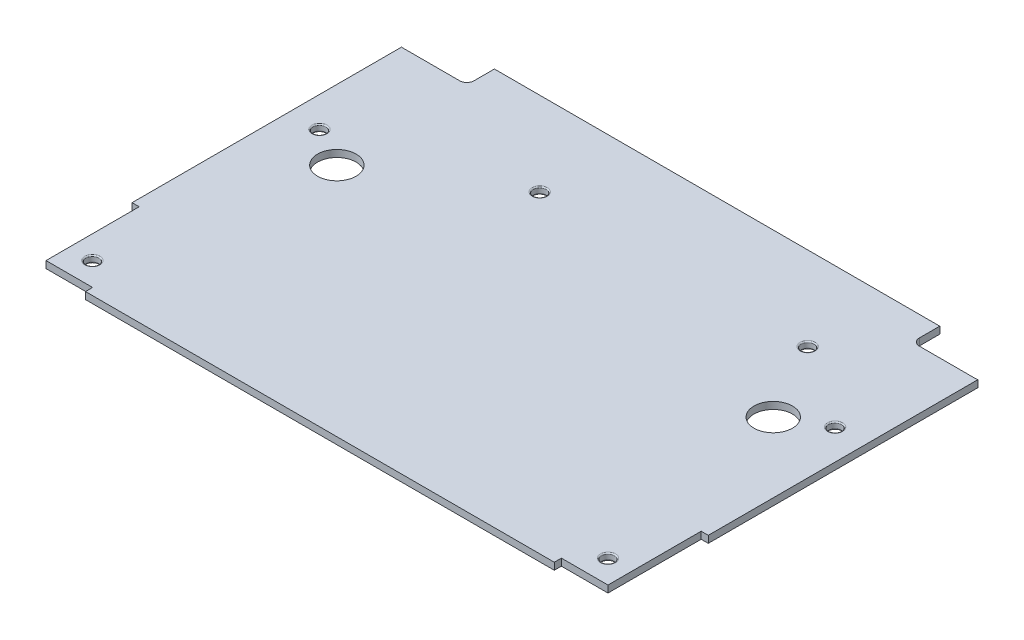
SolidWorks part; units mm, degrees
ref_plane "Front Plane" through (0, 0, 0) normal (0, 0, 1) x (1, 0, 0)
ref_plane "Top Plane" through (0, 0, 0) normal (0, 1, 0) x (1, 0, 0)
ref_plane "Right Plane" through (0, 0, 0) normal (1, 0, 0) x (0, 0, -1)
sketch "Sketch1" plane through (0, 0, 0) normal (0, 1, 0) x (1, 0, 0)
  line L1 (-123.65, -85.2375) -> (123.65, -85.2375)
  line L2 (-123.65, -85.2375) -> (-123.65, 85.2375)
  line L3 (-123.65, 85.2375) -> (123.65, 85.2375)
  line L4 (123.65, -85.2375) -> (123.65, 85.2375)
  line L5 (-123.65, -85.2375) -> (123.65, 85.2375) construction
  line L6 (-123.65, 85.2375) -> (123.65, -85.2375) construction
  point P0 (0, 0)
  dimension "D1" = 247.3
  dimension "D2" = 170.475
extrude "Boss-Extrude1" add sketch "Sketch1" along normal blind 3
sketch "Sketch4" plane through (0, 3, 0) normal (0, 1, 0) x (1, 0, 0)
  line L0 (0, 0) -> (0, -50000) construction
  line L5 (120.6, -82.1875) -> (100.6, -85.2375) construction
  line L15 (-123.65, -85.2375) -> (-120.6, -85.2375)
  line L16 (-123.65, -85.2375) -> (-123.65, -42.1875)
  line L21 (-123.65, -42.1875) -> (-120.6, -42.1875)
  line L23 (-120.6, -82.1875) -> (-120.6, -42.1875)
  line L24 (-123.65, -85.2375) -> (-120.6, -42.1875) construction
  line L25 (-123.65, -42.1875) -> (-120.6, -85.2375) construction
  line L34 (0, 0) -> (50000, 0) construction
  line L35 (-120.6, -85.2375) -> (-100.6, -85.2375)
  line L37 (-120.6, -82.1875) -> (-100.6, -82.1875)
  line L38 (-100.6, -85.2375) -> (-100.6, -82.1875)
  line L39 (-120.6, -85.2375) -> (-100.6, -82.1875) construction
  line L40 (-120.6, -82.1875) -> (-100.6, -85.2375) construction
  line L41 (120.6, -85.2375) -> (100.6, -82.1875) construction
  line L42 (123.65, -42.1875) -> (120.6, -85.2375) construction
  line L43 (123.65, -85.2375) -> (120.6, -42.1875) construction
  line L44 (100.6, -85.2375) -> (100.6, -82.1875)
  line L45 (120.6, -82.1875) -> (100.6, -82.1875)
  line L46 (120.6, -85.2375) -> (100.6, -85.2375)
  line L47 (120.6, -82.1875) -> (120.6, -42.1875)
  line L48 (123.65, -42.1875) -> (120.6, -42.1875)
  line L49 (123.65, -85.2375) -> (123.65, -42.1875)
  line L50 (123.65, -85.2375) -> (120.6, -85.2375)
  point P4 (-122.125, -63.7125)
  point P9 (-110.6, -83.7125)
  point P19 (110.6, -83.7125)
  point P20 (122.125, -63.7125)
  dimension "D1" = 43.05
  dimension "D2" = 3.05
  dimension "D3" = 3.05
  dimension "D4" = 23.05
extrude "Cut-Extrude2" cut sketch "Sketch4" against normal through all
sketch "Sketch2" plane through (0, 3, 0) normal (0, 1, 0) x (1, 0, 0)
  line L0 (0, 0) -> (50000, 0) construction
  line L1 (0, 0) -> (0, 50000) construction
  line L2 (-123.65, 85.2375) -> (-123.65, -42.1875) construction
  line L3 (123.65, 85.2375) -> (-123.65, 85.2375) construction
  line L4 (-100.6, -85.2375) -> (100.6, -85.2375) construction
  circle A0 centre (-110.65, 25.2375) radius 2.75
  circle A1 centre (110.65, 25.2375) radius 2.75
  circle A4 centre (-110.65, -72.2375) radius 2.75
  circle A5 centre (110.65, -72.2375) radius 2.75
  dimension "D1" = 5.5
  dimension "D2" = 13
  dimension "D3" = 60
  dimension "D4" = 13
extrude "Cut-Extrude1" cut sketch "Sketch2" against normal through all
fillet "Fillet1" radius 0.5 8 edges at (-110.65, 3, -22.4875) (-110.65, 0, -22.4875) (110.65, 3, -27.9875) (110.65, 0, -27.9875) (-110.65, 3, 74.9875) (-110.65, 0, 74.9875) (110.65, 3, 69.4875) (110.65, 0, 69.4875)
sketch "Sketch5" plane through (0, 3, 0) normal (0, 1, 0) x (1, 0, 0)
  line L5 (-10, 35.175) -> (10, 35.175)
  line L6 (15.05, 40.225) -> (15.05, 85.2375)
  line L8 (-15.05, 85.2375) -> (-15.05, 40.225)
  line L9 (-10, 35.225) -> (10, 35.225)
  line L10 (15, 40.225) -> (15, 92.225)
  line L11 (15, 92.225) -> (-15, 92.225)
  line L12 (-15, 92.225) -> (-15, 40.225)
  line L13 (-10, 35.225) -> (10, 35.225) construction
  line L14 (15, 40.225) -> (15, 92.225) construction
  line L15 (15, 92.225) -> (-15, 92.225) construction
  line L16 (-15, 92.225) -> (-15, 40.225) construction
  line L17 (15.05, 92.275) -> (-15.05, 92.275) construction
  line L18 (-15.05, 85.2375) -> (15.05, 85.2375)
  line L19 (123.65, 85.2375) -> (-123.65, 85.2375) construction
  line L20 (15.05, 40.225) -> (15.05, 92.275) construction
  line L21 (-15.05, 92.275) -> (-15.05, 40.225) construction
  arc A2 (10, 35.175) -> (15.05, 40.225) centre (10, 40.225) ccw
  arc A3 (-15.05, 40.225) -> (-10, 35.175) centre (-10, 40.225) ccw
  arc A4 (10, 35.225) -> (15, 40.225) centre (10, 40.225) ccw
  arc A5 (-15, 40.225) -> (-10, 35.225) centre (-10, 40.225) ccw
  arc A6 (10, 35.225) -> (15, 40.225) centre (10, 40.225) ccw construction
  arc A7 (-15, 40.225) -> (-10, 35.225) centre (-10, 40.225) ccw construction
  dimension "D1" = 0
  dimension "D2" = 0.05
extrude "Cut-Extrude3" [suppressed] cut sketch "Sketch5" against normal through all
sketch "Sketch6" [suppressed] plane through (0, 3, 0) normal (0, 1, 0) x (1, 0, 0)
  line L0 (-123.65, 105.2375) -> (-123.65, -62.1875) construction
  line L1 (-123.65, -72.4875) -> (-98.57, -72.4875)
  line L2 (-123.65, -72.4875) -> (-123.65, -8.8875)
  line L3 (-123.65, -8.8875) -> (-98.57, -8.8875)
  line L4 (-95.57, -69.4875) -> (-95.57, -11.8875)
  line L5 (-100.6, -105.2375) -> (100.6, -105.2375) construction
  line L6 (0, 0) -> (0, -50000) construction
  line L7 (95.57, -69.4875) -> (95.57, -11.8875)
  line L8 (123.65, -8.8875) -> (98.57, -8.8875)
  line L9 (123.65, -72.4875) -> (123.65, -8.8875)
  line L10 (123.65, -72.4875) -> (98.57, -72.4875)
  arc A0 (98.57, -72.4875) -> (95.57, -69.4875) centre (98.57, -69.4875) cw
  arc A1 (95.57, -11.8875) -> (98.57, -8.8875) centre (98.57, -11.8875) cw
  arc A2 (-98.57, -72.4875) -> (-95.57, -69.4875) centre (-98.57, -69.4875) ccw
  arc A3 (-95.57, -11.8875) -> (-98.57, -8.8875) centre (-98.57, -11.8875) ccw
  point P17 (95.57, -72.4875)
  point P20 (95.57, -8.8875)
  point P23 (-95.57, -72.4875)
  point P26 (-95.57, -8.8875)
  dimension "D4" = 3
  dimension "D1" = 32.75
  dimension "D2" = 63.6
  dimension "D3" = 28.08
extrude "Cut-Extrude4" [suppressed] cut sketch "Sketch6" against normal through all
sketch "Sketch8" [suppressed] plane through (0, 3, 0) normal (0, 1, 0) x (1, 0, 0)
  line L0 (-14.35, -33.2375) -> (-14.35, 49966.7625) construction
  line L1 (53.65, -55.2375) -> (-82.35, -55.2375) construction
  line L2 (53.65, -55.2375) -> (53.65, -11.2375) construction
  line L3 (53.65, -11.2375) -> (-82.35, -11.2375) construction
  line L4 (-82.35, -55.2375) -> (-82.35, -11.2375) construction
  line L5 (53.65, -55.2375) -> (-82.35, -11.2375) construction
  line L6 (53.65, -11.2375) -> (-82.35, -55.2375) construction
  line L7 (-14.35, -33.2375) -> (-50014.35, -33.2375) construction
  circle A0 centre (19.65, -55.2375) radius 1.5
  circle A1 centre (-14.35, -55.2375) radius 1.5
  circle A2 centre (-48.35, -55.2375) radius 1.5
  circle A3 centre (-48.35, -11.2375) radius 1.5
  circle A4 centre (-14.35, -11.2375) radius 1.5
  circle A5 centre (19.65, -11.2375) radius 1.5
  point P4 (-14.35, -33.2375)
  dimension "D1" = 3
  dimension "D3" = 34
extrude "Cut-Extrude6" [suppressed] cut sketch "Sketch8" against normal through all
fillet "Fillet2" [suppressed] radius 0.5
sketch "Sketch9" [suppressed] plane through (0, 3, 0) normal (0, 1, 0) x (1, 0, 0)
  circle A2 centre (-74.85, 26.2625) radius 2.75 construction
  circle A5 centre (40.15, 26.2625) radius 2.75 construction
  circle A8 centre (-74.85, 26.2625) radius 2.75
  circle A11 centre (40.15, 26.2625) radius 2.75
extrude "Cut-Extrude7" [suppressed] cut sketch "Sketch9" against normal through all
fillet "Fillet3" [suppressed] radius 0.5
sketch "Sketch10" plane through (0, 3, 0) normal (0, 1, 0) x (1, 0, 0)
  circle A0 centre (74.85, 49.2625) radius 2.75 construction
  circle A1 centre (-40.15, 49.2625) radius 2.75 construction
  circle A2 centre (74.85, 49.2625) radius 2.75
  circle A3 centre (-40.15, 49.2625) radius 2.75
extrude "Cut-Extrude8" cut sketch "Sketch10" against normal through all
fillet "Fillet4" radius 0.5 4 edges at (-40.15, 3, -46.5125) (-40.15, 0, -46.5125) (74.85, 3, -46.5125) (74.85, 0, -46.5125)
sketch "Sketch11" [suppressed] plane through (0, 3, 0) normal (0, 1, 0) x (1, 0, 0)
  line L0 (-123.65, 43.775) -> (-123.65, -0.725) construction
  line L1 (-83.65, 14.225) -> (-33.65, 14.225)
  line L6 (-83.65, 14.225) -> (-83.65, -35.775)
  line L8 (-83.65, -35.775) -> (-33.65, -35.775)
  line L9 (-33.65, 14.225) -> (-33.65, -35.775)
  line L10 (-83.65, 14.225) -> (-33.65, -35.775) construction
  line L11 (-83.65, -35.775) -> (-33.65, 14.225) construction
  circle A8 centre (-78.65, -30.775) radius 2.75
  circle A9 centre (-110.65, -30.775) radius 2.75 construction
  circle A10 centre (-110.65, -30.775) radius 2.75 construction
  circle A11 centre (-78.65, 9.225) radius 2.75
  circle A12 centre (-38.65, 9.225) radius 2.75
  circle A13 centre (-38.65, -30.775) radius 2.75
  point P4 (-58.65, -10.775)
  point P21 (-58.65, -10.775)
  dimension "D3" = 5
  dimension "D4" = 5.5
  dimension "D1" = 50
  dimension "D2" = 40
  dimension "D5" = 4
extrude "Cut-Extrude9" [suppressed] cut sketch "Sketch11" against normal through all contours A11 | A8 | A13 | A12
fillet "Fillet5" [suppressed] radius 0.5
sketch "Sketch12" [suppressed] plane through (0, 0, 0) normal (0, -1, 0) x (1, 0, 0)
  line L0 (0, 0) -> (0, 50000) construction
  line L4 (98.625, -155.4145) -> (122.675, -155.4145)
  line L5 (125.675, -152.4145) -> (125.675, -94.9145)
  line L6 (122.675, -91.9145) -> (98.625, -91.9145)
  line L7 (95.625, -94.9145) -> (95.625, -152.4145)
  line L9 (125.675, -105.2375) -> (125.675, -94.9145) construction
  line L10 (122.675, -91.9145) -> (98.625, -91.9145) construction
  line L11 (95.625, -94.9145) -> (95.625, -105.2375) construction
  line L12 (123.65, -105.2375) -> (-123.65, -105.2375) construction
  line L13 (123.65, -105.2375) -> (-123.65, -105.2375) construction
  line L15 (125.725, -105.2375) -> (125.725, -94.9145)
  line L16 (122.675, -91.8645) -> (98.625, -91.8645)
  line L17 (95.575, -94.9145) -> (95.575, -105.2375)
  line L18 (95.625, -105.2375) -> (125.675, -105.2375) construction
  line L19 (95.575, -105.2875) -> (125.725, -105.2875) construction
  line L20 (95.575, -105.2375) -> (125.725, -105.2375)
  line L21 (125.725, -105.2875) -> (125.725, -94.9145) construction
  line L22 (95.575, -94.9145) -> (95.575, -105.2875) construction
  line L23 (95.625, -152.4145) -> (95.625, -94.9145) construction
  line L24 (-95.625, -94.9145) -> (-95.625, -105.2375) construction
  line L25 (-122.675, -91.9145) -> (-98.625, -91.9145) construction
  line L26 (-125.675, -105.2375) -> (-125.675, -94.9145) construction
  line L27 (-95.575, -105.2375) -> (-125.725, -105.2375)
  line L28 (-95.575, -94.9145) -> (-95.575, -105.2375)
  line L29 (-122.675, -91.8645) -> (-98.625, -91.8645)
  line L30 (-125.725, -105.2375) -> (-125.725, -94.9145)
  arc A0 (125.725, -94.9145) -> (122.675, -91.8645) centre (122.675, -94.9145) ccw
  arc A1 (98.625, -91.8645) -> (95.575, -94.9145) centre (98.625, -94.9145) ccw
  arc A2 (-98.625, -91.9145) -> (-95.625, -94.9145) centre (-98.625, -94.9145) cw construction
  arc A3 (-125.675, -94.9145) -> (-122.675, -91.9145) centre (-122.675, -94.9145) cw construction
  arc A4 (122.675, -155.4145) -> (125.675, -152.4145) centre (122.675, -152.4145) ccw
  arc A5 (125.675, -94.9145) -> (122.675, -91.9145) centre (122.675, -94.9145) ccw
  arc A6 (98.625, -91.9145) -> (95.625, -94.9145) centre (98.625, -94.9145) ccw
  arc A7 (95.625, -152.4145) -> (98.625, -155.4145) centre (98.625, -152.4145) ccw
  arc A9 (125.675, -94.9145) -> (122.675, -91.9145) centre (122.675, -94.9145) ccw construction
  arc A10 (98.625, -91.9145) -> (95.625, -94.9145) centre (98.625, -94.9145) ccw construction
  arc A12 (-98.625, -91.8645) -> (-95.575, -94.9145) centre (-98.625, -94.9145) cw
  arc A13 (-125.725, -94.9145) -> (-122.675, -91.8645) centre (-122.675, -94.9145) cw
  dimension "D1" = 0
  dimension "D2" = 0.05
extrude "Cut-Extrude10" [suppressed] cut sketch "Sketch12" against normal through all
sketch "Sketch13" plane through (0, 0, 0) normal (0, -1, 0) x (1, 0, 0)
  line L0 (122.675, -73.4645) -> (98.625, -73.4645) construction
  line L1 (95.625, -76.4645) -> (95.625, -133.9645) construction
  line L2 (98.625, -136.9645) -> (122.675, -136.9645) construction
  line L3 (125.675, -133.9645) -> (125.675, -76.4645) construction
  line L4 (-98.625, -73.4645) -> (-122.675, -73.4645) construction
  line L5 (-125.675, -76.4645) -> (-125.675, -133.9645) construction
  line L6 (-122.675, -136.9645) -> (-98.625, -136.9645) construction
  line L7 (-95.625, -133.9645) -> (-95.625, -76.4645) construction
  line L8 (122.675, -73.4645) -> (98.625, -73.4645) construction
  line L9 (95.625, -76.4645) -> (95.625, -133.9645) construction
  line L10 (98.625, -136.9645) -> (122.675, -136.9645) construction
  line L11 (125.675, -133.9645) -> (125.675, -76.4645) construction
  line L12 (-98.625, -73.4645) -> (-122.675, -73.4645) construction
  line L13 (-125.675, -76.4645) -> (-125.675, -133.9645) construction
  line L14 (-122.675, -136.9645) -> (-98.625, -136.9645) construction
  line L15 (-95.625, -133.9645) -> (-95.625, -76.4645) construction
  line L16 (122.675, -73.4145) -> (98.625, -73.4145)
  line L17 (95.575, -76.4645) -> (95.575, -133.9645)
  line L18 (98.625, -137.0145) -> (122.675, -137.0145)
  line L19 (125.725, -133.9645) -> (125.725, -76.4645)
  line L20 (-98.625, -73.4145) -> (-122.675, -73.4145)
  line L21 (-125.725, -76.4645) -> (-125.725, -133.9645)
  line L22 (-122.675, -137.0145) -> (-98.625, -137.0145)
  line L23 (-95.575, -133.9645) -> (-95.575, -76.4645)
  arc A0 (98.625, -73.4645) -> (95.625, -76.4645) centre (98.625, -76.4645) ccw construction
  arc A1 (95.625, -133.9645) -> (98.625, -136.9645) centre (98.625, -133.9645) ccw construction
  arc A2 (122.675, -136.9645) -> (125.675, -133.9645) centre (122.675, -133.9645) ccw construction
  arc A3 (125.675, -76.4645) -> (122.675, -73.4645) centre (122.675, -76.4645) ccw construction
  arc A4 (-122.675, -73.4645) -> (-125.675, -76.4645) centre (-122.675, -76.4645) ccw construction
  arc A5 (-125.675, -133.9645) -> (-122.675, -136.9645) centre (-122.675, -133.9645) ccw construction
  arc A6 (-98.625, -136.9645) -> (-95.625, -133.9645) centre (-98.625, -133.9645) ccw construction
  arc A7 (-95.625, -76.4645) -> (-98.625, -73.4645) centre (-98.625, -76.4645) ccw construction
  arc A8 (98.625, -73.4645) -> (95.625, -76.4645) centre (98.625, -76.4645) ccw construction
  arc A9 (95.625, -133.9645) -> (98.625, -136.9645) centre (98.625, -133.9645) ccw construction
  arc A10 (122.675, -136.9645) -> (125.675, -133.9645) centre (122.675, -133.9645) ccw construction
  arc A11 (125.675, -76.4645) -> (122.675, -73.4645) centre (122.675, -76.4645) ccw construction
  arc A12 (-122.675, -73.4645) -> (-125.675, -76.4645) centre (-122.675, -76.4645) ccw construction
  arc A13 (-125.675, -133.9645) -> (-122.675, -136.9645) centre (-122.675, -133.9645) ccw construction
  arc A14 (-98.625, -136.9645) -> (-95.625, -133.9645) centre (-98.625, -133.9645) ccw construction
  arc A15 (-95.625, -76.4645) -> (-98.625, -73.4645) centre (-98.625, -76.4645) ccw construction
  arc A16 (98.625, -73.4145) -> (95.575, -76.4645) centre (98.625, -76.4645) ccw
  arc A17 (95.575, -133.9645) -> (98.625, -137.0145) centre (98.625, -133.9645) ccw
  arc A18 (122.675, -137.0145) -> (125.725, -133.9645) centre (122.675, -133.9645) ccw
  arc A19 (125.725, -76.4645) -> (122.675, -73.4145) centre (122.675, -76.4645) ccw
  arc A20 (-122.675, -73.4145) -> (-125.725, -76.4645) centre (-122.675, -76.4645) ccw
  arc A21 (-125.725, -133.9645) -> (-122.675, -137.0145) centre (-122.675, -133.9645) ccw
  arc A22 (-98.625, -137.0145) -> (-95.575, -133.9645) centre (-98.625, -133.9645) ccw
  arc A23 (-95.575, -76.4645) -> (-98.625, -73.4145) centre (-98.625, -76.4645) ccw
  dimension "D1" = 0.05
extrude "Cut-Extrude11" cut sketch "Sketch13" against normal through all
sketch "Sketch14" plane through (0, 3, 0) normal (0, 1, 0) x (1, 0, 0)
  line L0 (-123.65, 73.5745) -> (-123.65, -42.1875) construction
  line L1 (-96.15, 30.6935) -> (-91.15, 30.6935) construction
  line L2 (-101.15, 25.6935) -> (-101.15, 5.6935) construction
  line L3 (-96.15, 0.6935) -> (-91.15, 0.6935) construction
  line L4 (-86.15, 25.6935) -> (-86.15, 5.6935) construction
  line L5 (-101.15, 30.6935) -> (-86.15, 0.6935) construction
  line L6 (-101.15, 0.6935) -> (-86.15, 30.6935) construction
  line L7 (0, -1.65) -> (0, 1.65) construction
  line L8 (101.15, 0.6935) -> (86.15, 30.6935) construction
  line L9 (101.15, 30.6935) -> (86.15, 0.6935) construction
  line L10 (86.15, 25.6935) -> (86.15, 5.6935) construction
  line L11 (96.15, 0.6935) -> (91.15, 0.6935) construction
  line L12 (101.15, 25.6935) -> (101.15, 5.6935) construction
  line L13 (96.15, 30.6935) -> (91.15, 30.6935) construction
  arc A0 (-101.15, 5.6935) -> (-96.15, 0.6935) centre (-96.15, 5.6935) ccw construction
  arc A1 (-91.15, 0.6935) -> (-86.15, 5.6935) centre (-91.15, 5.6935) ccw construction
  arc A2 (-86.15, 25.6935) -> (-91.15, 30.6935) centre (-91.15, 25.6935) ccw construction
  arc A3 (-96.15, 30.6935) -> (-101.15, 25.6935) centre (-96.15, 25.6935) ccw construction
  arc A4 (96.15, 30.6935) -> (101.15, 25.6935) centre (96.15, 25.6935) cw construction
  arc A5 (86.15, 25.6935) -> (91.15, 30.6935) centre (91.15, 25.6935) cw construction
  arc A6 (91.15, 0.6935) -> (86.15, 5.6935) centre (91.15, 5.6935) cw construction
  arc A7 (101.15, 5.6935) -> (96.15, 0.6935) centre (96.15, 5.6935) cw construction
  circle A8 centre (-93.65, 15.6935) radius 8.255
  circle A10 centre (93.65, 15.6935) radius 8.255
  point P4 (-93.65, 15.6935)
  point P7 (-123.65, 15.6935)
  point P38 (123.65, 15.6935)
  point P39 (93.65, 15.6935)
  dimension "D4" = 5
  dimension "D5" = 16.51
  dimension "D1" = 30
  dimension "D2" = 15
  dimension "D3" = 30
extrude "Cut-Extrude12" cut sketch "Sketch14" against normal through all
